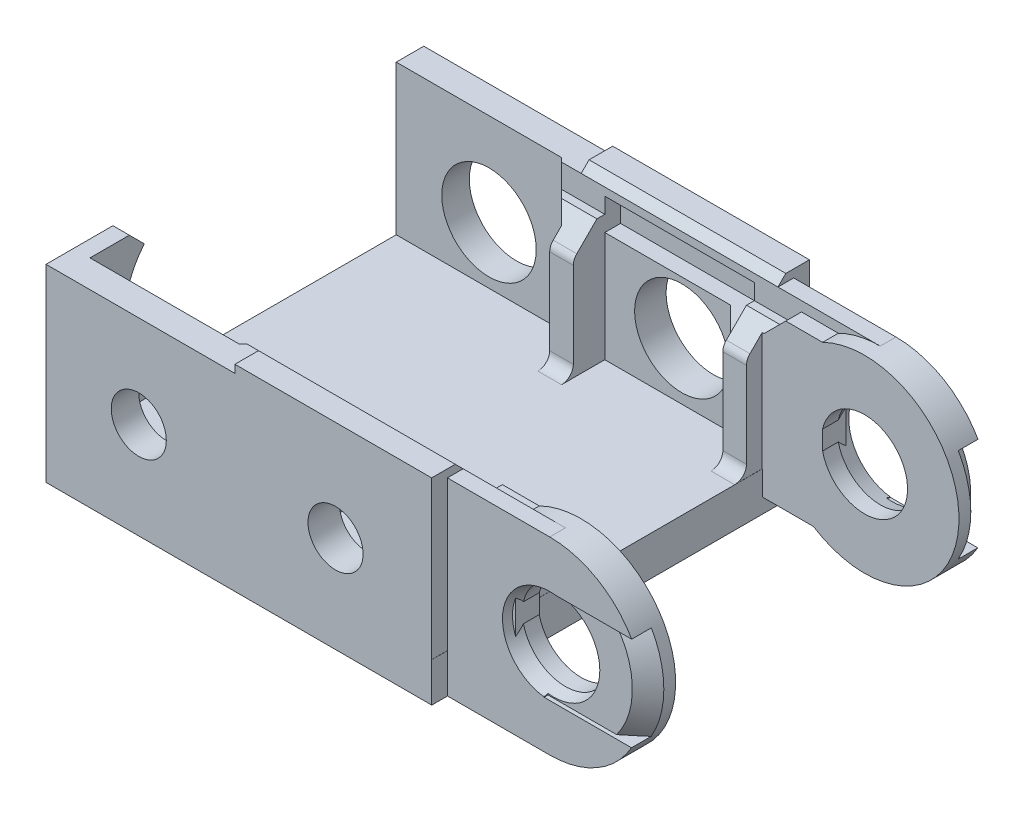
SolidWorks part; units mm, degrees
ref_plane "Front" through (0, 0, 0) normal (0, 0, 1) x (1, 0, 0)
ref_plane "Top" through (0, 0, 0) normal (0, 1, 0) x (1, 0, 0)
ref_plane "Right" through (0, 0, 0) normal (1, 0, 0) x (0, 0, -1)
sketch "Эскиз1" plane through (0, 0, 0) normal (0, 0, 1) x (1, 0, 0)
  line L1 (-38.7795, 23.7195) -> (-13.7795, 23.7195)
  line L2 (-38.7795, 23.7195) -> (-38.7795, -1.2805)
  line L3 (-38.7795, -1.2805) -> (-13.7795, -1.2805)
  line L4 (-13.7795, 23.7195) -> (-13.7795, -1.2805)
  dimension "D1" = 25
  dimension "D2" = 25
extrude "Бобышка-Вытянуть1" add sketch "Эскиз1" along normal blind 4
sketch "Эскиз2" plane through (0, 0, 0) normal (0, 0, -1) x (-1, 0, 0)
  line L0 (38.7795, 22.7195) -> (62.7795, 22.7195)
  line L1 (38.7795, 23.7195) -> (38.7795, -1.2805) construction
  line L3 (62.7795, 22.7195) -> (62.7795, -1.2805)
  line L4 (62.7795, -1.2805) -> (38.7795, -1.2805)
  line L5 (38.7795, -1.2805) -> (38.7795, 22.7195)
  dimension "D1" = 24
  dimension "D2" = 24
extrude "Бобышка-Вытянуть2" add sketch "Эскиз2" against normal blind 3.5
sketch "Эскиз3" plane through (0, 0, 3.5) normal (0, 0, 1) x (1, 0, 0)
  line L1 (-38.7795, -1.2805) -> (-62.7795, -1.2805) construction
  line L2 (-62.7795, -1.2805) -> (-62.7795, 22.7195) construction
  circle A0 centre (-50.7795, 10.7195) radius 5.625
  dimension "D2" = 11.25
  dimension "D1" = 12
  dimension "D3" = 12
sketch "Эскиз5" plane through (0, 0, 4) normal (0, 0, 1) x (1, 0, 0)
  line L0 (-18.982, 10.7195) -> (-0.7795, 10.7195) construction
  line L1 (-18.982, 22.7195) -> (-0.7795, 22.7195)
  line L2 (-18.982, -1.2805) -> (-0.7795, -1.2805)
  line L3 (-13.7795, -1.2805) -> (-13.7795, 23.7195) construction
  line L4 (-38.7795, -1.2805) -> (-13.7795, -1.2805) construction
  arc A0 (-18.982, 22.7195) -> (-18.982, -1.2805) centre (-18.982, 10.7195) ccw
  arc A1 (-0.7795, -1.2805) -> (-0.7795, 22.7195) centre (-0.7795, 10.7195) ccw
  point P2 (-9.8808, 10.7195)
  dimension "D1" = 13
  dimension "D2" = 12
  dimension "D3" = 12
extrude "Бобышка-Вытянуть4" add sketch "Эскиз5" against normal blind 2
sketch "Эскиз6" plane through (0, 0, 2) normal (0, 0, -1) x (-1, 0, 0)
  circle A0 centre (0.7795, 10.7195) radius 5
  arc A1 (0.7795, 22.7195) -> (0.7795, -1.2805) centre (0.7795, 10.7195) ccw construction
extrude "Вырез-Вытянуть2" cut sketch "Эскиз6" against normal blind 10
sketch "Эскиз8" plane through (0, 0, 4) normal (0, 0, 1) x (1, 0, 0)
  line L5 (-38.7795, 3.7195) -> (-35.7795, 3.7195)
  line L6 (-38.7795, -1.2805) -> (-13.7795, -1.2805)
  line L7 (-38.7795, -1.2805) -> (-38.7795, 3.7195)
  line L9 (-13.7795, -1.2805) -> (-13.7795, 3.7195)
  line L10 (-35.7795, 3.7195) -> (-35.7795, 0.7195)
  line L11 (-35.7795, 0.7195) -> (-16.7795, 0.7195)
  line L12 (-16.7795, 0.7195) -> (-16.7795, 3.7195)
  line L13 (-16.7795, 3.7195) -> (-13.7795, 3.7195)
  line L14 (-13.7795, 22.7195) -> (-13.7795, 23.7195) construction
  dimension "D1" = 3
  dimension "D2" = 3
  dimension "D3" = 2
  dimension "D4" = 5
  dimension "D5" = 5
extrude "Бобышка-Вытянуть6" add sketch "Эскиз8" along normal blind 20
sketch "Эскиз9" plane through (0, 0, 4) normal (0, 0, 1) x (1, 0, 0)
  line L0 (-38.7795, 23.7195) -> (-38.7795, 3.7195) construction
  line L1 (-35.7795, 20.7195) -> (-16.7795, 20.7195)
  line L2 (-35.7795, 20.7195) -> (-35.7795, 17.7195)
  line L3 (-35.7795, 17.7195) -> (-16.7795, 17.7195)
  line L4 (-16.7795, 20.7195) -> (-16.7795, 17.7195)
  line L5 (-13.7795, 22.7195) -> (-13.7795, 23.7195) construction
  line L6 (-13.7795, 23.7195) -> (-38.7795, 23.7195) construction
  dimension "D1" = 3
  dimension "D2" = 3
  dimension "D3" = 3
  dimension "D4" = 6
extrude "Вырез-Вытянуть4" cut sketch "Эскиз9" against normal blind 2
chamfer "Фаска2" distance 1 angle 45 1 edges at (-26.2795, 20.7195, 4)
chamfer "Фаска3" distance 1 angle 75 1 edges at (-5.7795, 10.7195, 2) first distance on face at (-5.7795, 10.7195, 2)
chamfer "Фаска4" distance 1 angle 45 1 edges at (-26.2795, 23.7195, 4)
sketch "Эскиз11" plane through (0, 3.7195, 0) normal (0, 1, 0) x (1, 0, 0)
  line L0 (-35.7795, -24) -> (-35.7795, -4) construction
  line L1 (-38.7795, -4) -> (-35.7795, -4)
  line L2 (-38.7795, -4) -> (-38.7795, -8)
  line L3 (-38.7795, -8) -> (-35.7795, -8)
  line L4 (-35.7795, -4) -> (-35.7795, -8)
  dimension "D1" = 4
extrude "Бобышка-Вытянуть7" add sketch "Эскиз11" along normal blind 16
pattern_linear "Линейный массив1" count 2 spacing 22 along (1, 0, 0) of "Бобышка-Вытянуть7"
chamfer "Фаска6" distance 3 angle 45 2 edges at (-15.2795, 19.7195, 8) (-37.2795, 19.7195, 8)
fillet "Скругление2" radius 1.5 4 edges at (-15.2795, 3.7195, 8) (-15.2795, 16.7195, 8) (-37.2795, 16.7195, 8) (-37.2795, 3.7195, 8)
sketch "Эскиз13" plane through (0, 0, 4) normal (0, 0, 1) x (1, 0, 0)
  circle A0 centre (-50.993, 10.9769) radius 3.5
extrude "Вырез-Вытянуть6" cut sketch "Эскиз13" against normal blind 10
pattern_linear "Линейный массив2" count 2 spacing 25 along (1, 0, 0) of "Вырез-Вытянуть6"
chamfer "Фаска7" distance 3 angle 45 2 edges at (-38.7795, 10.7195, 3.5) (-16.7795, 9.2195, 4)
sketch "Эскиз16" plane through (0, 0, 4) normal (0, 0, 1) x (1, 0, 0)
  circle A0 centre (-0.7795, 10.7195) radius 5.4641
  circle A1 centre (-0.7795, 10.7195) radius 12
extrude "Бобышка-Вытянуть9" add sketch "Эскиз16" along normal blind 2
sketch "Эскиз17" plane through (0, 0, 6) normal (0, 0, 1) x (1, 0, 0)
  line L1 (-6.1084, 21.4714) -> (-13.7892, 21.4714)
  line L2 (-6.1084, 21.4714) -> (-6.1084, 0.6234)
  line L3 (-6.1084, 0.6234) -> (-13.7892, 0.6234)
  line L4 (-13.7892, 21.4714) -> (-13.7892, 0.6234)
  circle A0 centre (-0.7795, 10.7195) radius 12 construction
extrude "Бобышка-Вытянуть10" add sketch "Эскиз17" against normal blind 3
chamfer "Фаска8" distance 3 angle 45 1 edges at (-13.7892, 21.4714, 5)
sketch "Эскиз18" plane through (0, 0, 2) normal (0, 0, -1) x (-1, 0, 0)
  line L1 (1.5008, 16.676) -> (-12.7446, 16.676)
  line L2 (1.5008, 16.676) -> (1.5008, 4.7195)
  line L3 (1.5008, 4.7195) -> (-12.7446, 4.7195)
  line L4 (-12.7446, 16.676) -> (-12.7446, 4.7195)
  circle A0 centre (0.7795, 10.7195) radius 6 construction
extrude "Вырез-Вытянуть8" cut sketch "Эскиз18" against normal blind 0.5
chamfer "Фаска9" distance 2 angle 45 1 edges at (11.2204, 10.6944, 2.5)
mirror "Зеркальное отражение1" about plane through (0, 0, 24) normal (0, 0, -1) of bodies 121 109
sketch "Эскиз14" plane through (0, -1.2805, 0) normal (0, -1, 0) x (-1, 0, 0)
  line L0 (62.7795, 0) -> (13.7795, 0) construction
  line L1 (62.7795, -48) -> (13.768, -48)
  line L2 (62.7795, -48) -> (62.7795, 0)
  line L3 (62.7795, 0) -> (13.768, 0)
  line L4 (13.768, -48) -> (13.768, 0)
extrude "Бобышка-Вытянуть8" add sketch "Эскиз14" against normal blind 5
sketch "Эскиз15" plane through (0, 0, 0) normal (0, 0, -1) x (-1, 0, 0)
  circle A0 centre (50.993, 10.9769) radius 6
  circle A1 centre (25.993, 10.9769) radius 6
extrude "Вырез-Вытянуть7" cut sketch "Эскиз15" against normal blind 4
chamfer "Фаска10" distance 3 angle 45 2 edges at (-27.7795, 3.7195, 44) (-52.2795, 3.7195, 44.5)
sketch "Эскиз19" plane through (0, 0, 44.5) normal (0, 0, -1) x (-1, 0, 0)
  line L1 (62.7795, 22.7195) -> (60.6904, 22.7195)
  line L2 (62.7795, 22.7195) -> (62.7795, 0)
  line L3 (62.7795, 0) -> (60.6904, 0)
  line L4 (60.6904, 22.7195) -> (60.6904, 0)
extrude "Бобышка-Вытянуть11" add sketch "Эскиз19" along normal blind 15
chamfer "Фаска11" distance 10 angle 45 1 edges at (-61.735, 22.7195, 29.5)
sketch "Эскиз20" plane through (0, 0, 40) normal (0, 0, -1) x (-1, 0, 0)
  line L1 (13.7795, 16.0982) -> (16.8955, 16.0982)
  line L2 (13.7795, 16.0982) -> (13.7795, 2.3184)
  line L3 (13.7795, 2.3184) -> (16.8955, 2.3184)
  line L4 (16.8955, 16.0982) -> (16.8955, 2.3184)
  line L5 (35.7795, 16.0982) -> (38.95, 16.0982)
  line L6 (35.7795, 16.0982) -> (35.7795, 0.7032)
  line L7 (35.7795, 0.7032) -> (38.95, 0.7032)
  line L8 (38.95, 16.0982) -> (38.95, 0.7032)
extrude "Бобышка-Вытянуть12" add sketch "Эскиз20" along normal blind 10
sketch "Эскиз21" plane through (-13.7795, 0, 0) normal (1, 0, 0) x (0, 0, -1)
  line L0 (-30, 16.0982) -> (-30, 3.7195) construction
  circle A0 centre (-30, 14.2806) radius 10.018
extrude "Вырез-Вытянуть9" cut sketch "Эскиз21" against normal blind 100
